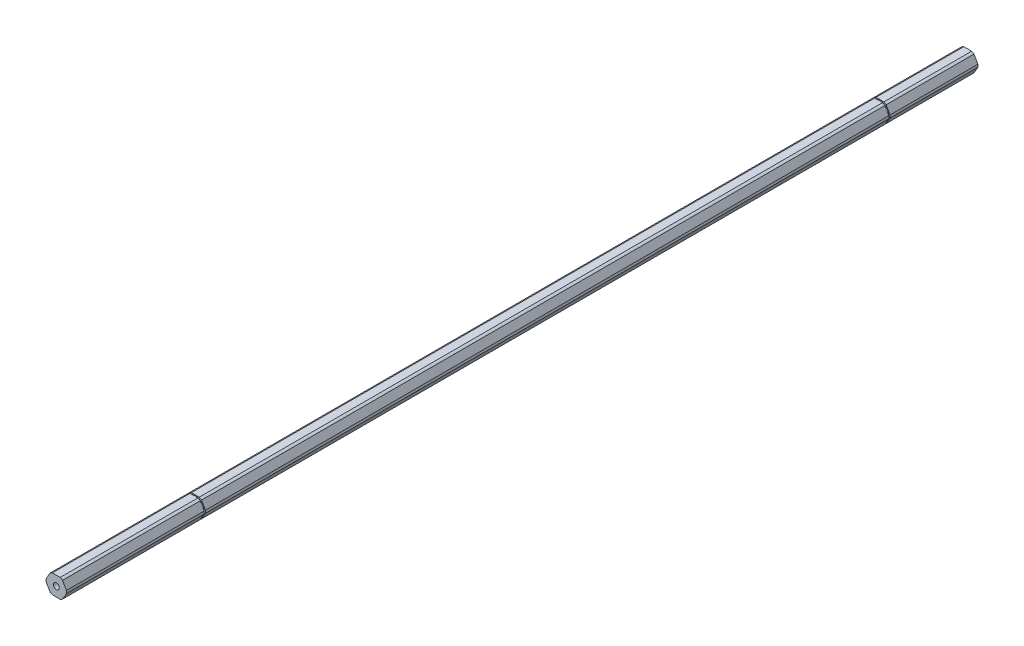
SolidWorks part; units mm, degrees
material "6061-T6 (SS)"
ref_plane "Front Plane" through (0, 0, 0) normal (0, 0, 1) x (1, 0, 0)
ref_plane "Top Plane" through (0, 0, 0) normal (0, 1, 0) x (1, 0, 0)
ref_plane "Right Plane" through (0, 0, 0) normal (1, 0, 0) x (0, 0, -1)
sketch "Sketch1" plane through (0, 0, 0) normal (0, 0, 1) x (1, 0, 0)
  line L1 (3.6662, 6.35) -> (-3.6662, 6.35)
  line L2 (-3.6662, 6.35) -> (-7.3323, 0)
  line L3 (-7.3323, 0) -> (-3.6662, -6.35)
  line L4 (-3.6662, -6.35) -> (3.6662, -6.35)
  line L5 (3.6662, -6.35) -> (7.3323, 0)
  line L6 (7.3323, 0) -> (3.6662, 6.35)
  circle A0 centre (0, 0) radius 6.35 construction
  circle A1 centre (0, 0) radius 6.875
  circle A2 centre (0, 0) radius 2
  point P1 (0, 6.35)
  dimension "D2" = 13.75
  dimension "D3" = 4
  dimension "D1" = 12.7
extrude "Boss-Extrude1" add sketch "Sketch1" along normal blind 609.6 contours L6 A1 L1 L2 L3 L4 L5 A2 region at (3.3439, 5.7918, 0)
sketch "Sketch2" plane through (0, 0, 0) normal (0, 1, 0) x (1, 0, 0)
  line L0 (2.635, -609.6) -> (-2.635, -609.6) construction
  line L1 (-5.8547, -516.636) -> (5.8547, -516.636)
  line L2 (-5.8547, -516.636) -> (-5.8547, -517.525)
  line L3 (-5.8547, -517.525) -> (5.8547, -517.525)
  line L4 (5.8547, -516.636) -> (5.8547, -517.525)
  line L5 (0, -609.6) -> (0, 0) construction
  line L6 (7.5057, -516.636) -> (-7.5057, -516.636)
  line L7 (7.5057, -516.636) -> (7.5057, -517.525)
  line L8 (7.5057, -517.525) -> (-7.5057, -517.525)
  line L9 (-7.5057, -516.636) -> (-7.5057, -517.525)
  line L10 (2.635, 0) -> (-2.635, 0) construction
  line L11 (-5.8547, -58.7375) -> (5.8547, -58.7375)
  line L12 (-5.8547, -58.7375) -> (-5.8547, -59.6265)
  line L13 (-5.8547, -59.6265) -> (5.8547, -59.6265)
  line L14 (5.8547, -58.7375) -> (5.8547, -59.6265)
  line L16 (5.8547, -58.7375) -> (7.5057, -58.7375)
  line L17 (5.8547, -58.7375) -> (5.8547, -59.6265)
  line L18 (5.8547, -59.6265) -> (7.5057, -59.6265)
  line L19 (7.5057, -58.7375) -> (7.5057, -59.6265)
  point P6 (0, -609.6)
  point P7 (0, -517.525)
  point P21 (0, -58.7375)
  dimension "D1" = 92.075
  dimension "D2" = 0.889
  dimension "D3" = 11.7094
  dimension "D4" = 1.651
  dimension "D5" = 1.651
  dimension "D6" = 58.7375
  dimension "D7" = 0.889
  dimension "D8" = 11.7094
  dimension "D9" = 1.651
revolve "Cut-Revolve1" cut sketch "Sketch2" angle 360 about L5 region at (6.6802, 0, 517.0805) region at (6.6802, 0, 59.182)
equation "\"D2@Sketch1\"=13.750000mm"
equation "\"D3@Sketch1\"=4mm"
equation "\"D5@Sketch2\"=\"D4@Sketch2\""
equation "\"D3@Sketch2\"=\"D8@Sketch2\""
